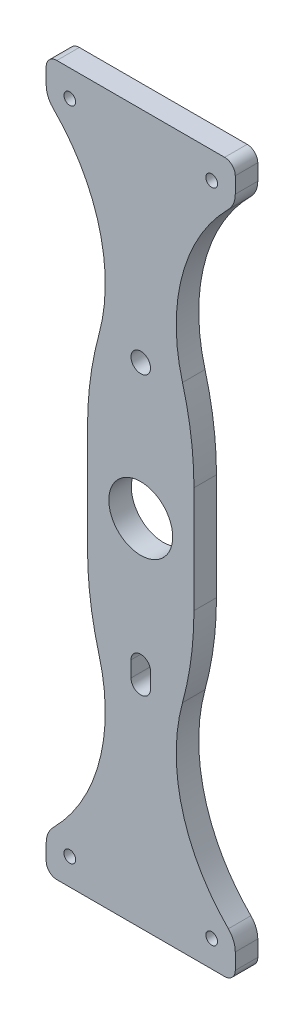
SolidWorks part; units mm, degrees
material "6061-T6 (SS)"
ref_plane "Front Plane" through (0, 0, 0) normal (0, 0, 1) x (1, 0, 0)
ref_plane "Top Plane" through (0, 0, 0) normal (0, 1, 0) x (1, 0, 0)
ref_plane "Right Plane" through (0, 0, 0) normal (1, 0, 0) x (0, 0, -1)
sketch "Sketch1" plane through (0, 0, 0) normal (0, 0, 1) x (1, 0, 0)
  line L5 (-15, 0) -> (15, 0) construction
  line L6 (0, -35.8891) -> (0, -40.3109) construction
  line L10 (2.75, -35.8891) -> (2.75, -40.3109)
  line L13 (240, 100) -> (240, -100) construction
  line L14 (-2.75, -35.8891) -> (-2.75, -40.3109)
  line L15 (-15, 15) -> (-15, -15)
  line L18 (-23.65, -100) -> (23.65, -100)
  line L21 (15, -15) -> (15, 15)
  line L23 (26.65, 92.5) -> (26.65, 97)
  line L24 (23.65, 100) -> (-23.65, 100)
  line L25 (-26.65, 97) -> (-26.65, 92.5)
  line L27 (26.65, -92.5) -> (26.65, -97)
  line L28 (-26.65, -97) -> (-26.65, -92.5)
  line L29 (-3.92, 79.4898) -> (-3.92, -120.5102) construction
  line L30 (0, 100) -> (0, 0) construction
  line L31 (-10, -52.3033) -> (-10, -92.5) construction
  line L32 (-10, -92.5) -> (10, -92.5) construction
  line L33 (10, -92.5) -> (10, -52.3033) construction
  line L34 (24.7023, 87.7977) -> (0, 63.0955) construction
  circle A0 centre (0, 0) radius 9
  circle A13 centre (0, 38.1) radius 4.9609 construction
  circle A14 centre (0, -38.1) radius 4.9609 construction
  circle A18 centre (0, 38.1) radius 2.75
  arc A19 (2.75, -35.8891) -> (-2.75, -35.8891) centre (0, -35.8891) ccw
  arc A20 (-2.75, -40.3109) -> (2.75, -40.3109) centre (0, -40.3109) ccw
  circle A21 centre (20, 92.5) radius 1.65
  circle A22 centre (-20, 92.5) radius 1.65
  circle A23 centre (-20, -92.5) radius 1.65
  circle A24 centre (20, -92.5) radius 1.65
  arc A25 (-26.65, 92.5) -> (-24.7023, 87.7977) centre (-20, 92.5) ccw
  arc A27 (26.65, 92.5) -> (24.7023, 87.7977) centre (20, 92.5) cw
  arc A29 (26.65, -92.5) -> (24.7023, -87.7977) centre (20, -92.5) ccw
  arc A32 (-26.65, -92.5) -> (-24.7023, -87.7977) centre (-20, -92.5) cw
  arc A33 (15, -15) -> (11.7718, -39.0845) centre (-76.4573, -15) cw
  arc A34 (11.7718, -39.0845) -> (24.7023, -87.7977) centre (60.1967, -52.3033) ccw
  arc A35 (-11.7718, -39.0845) -> (-24.7023, -87.7977) centre (-60.1967, -52.3033) cw
  arc A36 (-15, -15) -> (-11.7718, -39.0845) centre (76.4573, -15) ccw
  arc A37 (-15, 15) -> (-11.7718, 39.0845) centre (76.4573, 15) cw
  arc A38 (-11.7718, 39.0845) -> (-24.7023, 87.7977) centre (-60.1967, 52.3033) ccw
  arc A39 (11.7718, 39.0845) -> (24.7023, 87.7977) centre (60.1967, 52.3033) cw
  arc A40 (15, 15) -> (11.7718, 39.0845) centre (-76.4573, 15) ccw
  arc A42 (-23.65, 100) -> (-26.65, 97) centre (-23.65, 97) ccw
  arc A43 (26.65, 97) -> (23.65, 100) centre (23.65, 97) ccw
  arc A44 (-26.65, -97) -> (-23.65, -100) centre (-23.65, -97) ccw
  arc A45 (26.65, -97) -> (23.65, -100) centre (23.65, -97) cw
  point P6 (0, -38.1)
  point P48 (7.5, -92.5)
  point P49 (-3.92, 79.4898)
  point P64 (0, -92.5)
  point P65 (-24.9237, -88.0301)
  point P69 (-26.65, 100)
  point P72 (26.65, 100)
  point P75 (-26.65, -100)
  point P78 (26.65, -100)
  dimension "D1" = 18
  dimension "D9" = 9.9219
  dimension "D2" = 5.5
  dimension "D3" = 3.3
  dimension "D11" = 3
  dimension "D8" = 76.2
  dimension "D4" = 220
  dimension "D6" = 185
  dimension "D7" = 200
  dimension "D10" = 5
  dimension "D5" = 40
  dimension "D13" = 30
  dimension "D14" = 20
  dimension "D15" = 30
  dimension "D16" = 45
extrude "Boss-Extrude1" add sketch "Sketch1" along normal blind 6.35
sketch "Sketch2" plane through (0, 0, 0) normal (0, 0, -1) x (-1, 0, 0)
  line L0 (-15.2237, 74.6) -> (15.2237, 74.6)
  line L1 (-23.65, 100) -> (23.65, 100) construction
  line L2 (3.4925, 0) -> (-3.4925, 0) construction
  line L3 (-15.2237, -74.6) -> (15.2237, -74.6)
  arc A0 (24.7023, 87.7977) -> (11.7718, 39.0845) centre (60.1967, 52.3033) ccw construction
  arc A1 (-11.7718, 39.0845) -> (-24.7023, 87.7977) centre (-60.1967, 52.3033) ccw construction
  point P2 (13.2017, 69.9435)
  point P6 (-13.2017, 69.9435)
  dimension "D1" = 25.4
split line "Split Line1"
equation "\"frame inside height\" = 200mm'`"
equation "\"hole spacing\" = 20mm"
equation "\"top hole to bottom hole\"= \"frame inside height\" - 7.5mm * 2"
equation "\"D6@Sketch1\"=\"top hole to bottom hole\""
equation "\"D7@Sketch1\"=\"frame inside height\""
equation "\"D5@Sketch1\"=\"hole spacing\"*2"
